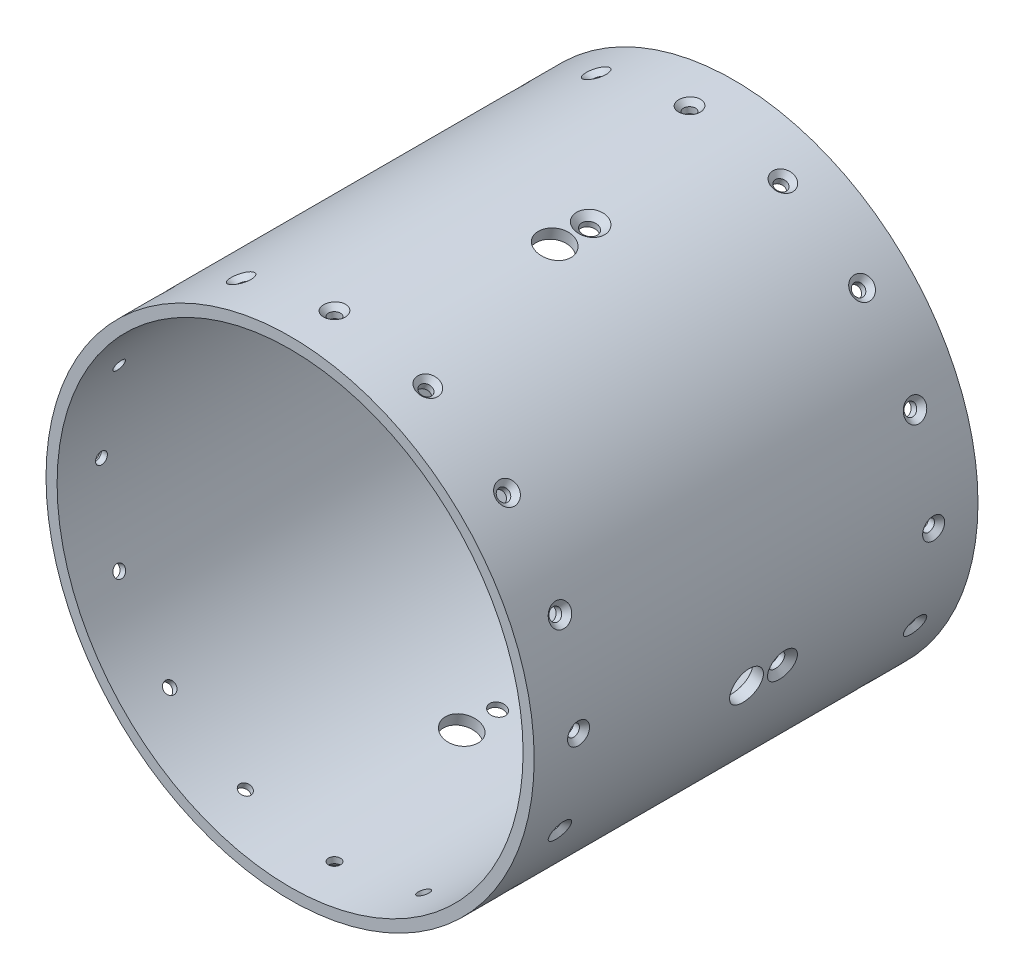
SolidWorks part; units mm, degrees
material "6061-T6 (SS)"
ref_plane "Front Plane" through (0, 0, 0) normal (0, 0, 1) x (1, 0, 0)
ref_plane "Top Plane" through (0, 0, 0) normal (0, 1, 0) x (1, 0, 0)
ref_plane "Right Plane" through (0, 0, 0) normal (1, 0, 0) x (0, 0, -1)
sketch "Sketch1" plane through (0, 0, 0) normal (0, 0, 1) x (1, 0, 0)
  circle A0 centre (0, 0) radius 66.675
  circle A1 centre (0, 0) radius 69.85
extrude "Extrude1" add sketch "Sketch1" along normal blind 127
sketch "Sketch4" plane through (0, 0, 0) normal (0, 0, -1) x (-1, 0, 0)
  circle A0 centre (0, 0) radius 66.675
sketch "Sketch5" plane through (0, 0, 127) normal (0, 0, 1) x (1, 0, 0)
  circle A0 centre (0, 0) radius 66.675
ref_plane "Plane1" through (0, 0, 12.7) normal (0, 0, 1) x (1, 0, 0)
ref_plane "Plane3" through (0, 0, 114.3) normal (0, 0, 1) x (1, 0, 0)
sketch "Sketch11" plane through (0, 0, 114.3) normal (0, 0, 1) x (1, 0, 0)
  line L0 (0, 0) -> (69.85, 0) construction
  circle A0 centre (0, 0) radius 69.85 construction
ref_plane "Plane4" through (69.85, 0, 114.3) normal (1, 0, 0) x (0, 0, -1)
hole_wizard "CSK for M3 Flat Head Machine Screw2" positions "Sketch13" profile "Sketch12" countersink size "M3" standard "Ansi Metric"
sketch "Sketch13" plane through (69.85, 0, 114.3) normal (1, 0, 0) x (0, 0, -1)
  point P1 (0, 0)
sketch "Sketch12" plane through (69.85, 0, 114.3) normal (0, 1, 0) x (0, 0, -1)
  line L0 (0, 0) -> (0, 13.2135)
  line L1 (0, 13.2135) -> (1.7, 12.192)
  line L2 (1.7, 12.192) -> (1.7, 1.45)
  line L3 (1.7, 1.45) -> (3.15, 0)
  line L5 (3.15, 0) -> (0, 0)
  line L6 (-1.7, 1.45) -> (-3.15, 0) construction
  line L10 (0, 13.2135) -> (-1.7, 12.192) construction
  line L11 (0, -6.35) -> (0, 107.95) construction
  dimension "Hole Dia." = 3.4
  dimension "Hole Depth" = 12.192
  dimension "Near C'Sink Dia." = 6.3
  dimension "Near C'Sink Angle" = 90
  dimension "Drill Angle" = 118
sketch "Sketch23" plane through (0, 0, 12.7) normal (0, 0, 1) x (1, 0, 0)
  line L0 (0, 0) -> (69.85, 0) construction
ref_plane "Plane7" through (69.85, 0, 12.7) normal (1, 0, 0) x (0, 0, -1)
hole_wizard "CSK for M3 Flat Head Machine Screw1" positions "Sketch29" profile "Sketch30" countersink size "M3" standard "Ansi Metric"
sketch "Sketch29" plane through (69.85, 0, 12.7) normal (1, 0, 0) x (0, 0, -1)
  point P1 (0, 0)
sketch "Sketch30" plane through (69.85, 0, 12.7) normal (0, 1, 0) x (0, 0, -1)
  line L0 (0, 0) -> (0, 13.2135)
  line L1 (0, 13.2135) -> (1.7, 12.192)
  line L2 (1.7, 12.192) -> (1.7, 1.45)
  line L3 (1.7, 1.45) -> (3.15, 0)
  line L5 (3.15, 0) -> (0, 0)
  line L6 (-1.7, 1.45) -> (-3.15, 0) construction
  line L10 (0, 13.2135) -> (-1.7, 12.192) construction
  line L11 (0, -6.35) -> (0, 107.95) construction
  dimension "Hole Dia." = 3.4
  dimension "Hole Depth" = 12.192
  dimension "Near C'Sink Dia." = 6.3
  dimension "Near C'Sink Angle" = 90
  dimension "Drill Angle" = 118
pattern_circular "CirPattern1" count 16 over 360 about axis through (0, 0, 127) along (0, 0, -1) of "CSK for M3 Flat Head Machine Screw2", "CSK for M3 Flat Head Machine Screw1"
ref_plane "Plane8" through (0, 0, 64.77) normal (0, 0, 1) x (1, 0, 0)
sketch "Sketch35" plane through (0, 0, 64.77) normal (0, 0, 1) x (1, 0, 0)
  line L0 (69.8153, 0) -> (68.4, 0) construction
  arc A0 (69.85, 0) -> (68.5079, -13.6271) centre (0, 0) cw
  circle A1 centre (0, 0) radius 69.85 construction
sketch "Sketch31" plane through (0, 0, 64.77) normal (0, 0, 1) x (1, 0, 0)
  line L0 (0, 0) -> (68.5079, -13.6271) construction
ref_plane "Plane6" through (68.5079, -13.6271, 64.77) normal (0.9808, -0.1951, 0) x (0.1951, 0.9808, 0)
sketch "Sketch15" plane through (68.5079, -13.6271, 64.77) normal (0.9808, -0.1951, 0) x (0.1951, 0.9808, 0)
  line L0 (0, 0.1207) -> (0, -10.16) construction
hole_wizard "3/8 (0.375) Diameter Hole1" positions "Sketch33" profile "Sketch32" hole size "3/8" standard "Ansi Inch"
sketch "Sketch33" plane through (68.5079, -13.6271, 64.77) normal (0.9808, -0.1951, 0) x (0.1951, 0.9808, 0)
  point P1 (0, 0.1207)
sketch "Sketch32" plane through (68.5079, -13.6271, 64.8907) normal (0, 0, 1) x (0.1951, 0.9808, 0)
  line L0 (0, 0) -> (0, 15.5616)
  line L1 (0, 15.5616) -> (4.7625, 12.7)
  line L2 (4.7625, 12.7) -> (4.7625, 0)
  line L5 (4.7625, 0) -> (0, 0)
  line L10 (0, 15.5616) -> (-4.7625, 12.7) construction
  line L11 (0, -6.35) -> (0, 107.95) construction
  dimension "Hole Dia." = 9.525
  dimension "Hole Depth" = 12.7
  dimension "Drill Angle" = 118
hole_wizard "CSK for #8 Flat Head Machine Screw (100)2" positions "Sketch21" profile "Sketch22" countersink size "#8" standard "Ansi Inch"
sketch "Sketch21" plane through (68.5079, -13.6271, 64.77) normal (0.9808, -0.1951, 0) x (0.1951, 0.9808, 0)
  point P1 (0, -10.16)
sketch "Sketch22" plane through (68.5079, -13.6271, 54.61) normal (0, 0, 1) x (0.1951, 0.9808, 0)
  line L0 (0, 0) -> (0, 13.5427)
  line L1 (0, 13.5427) -> (2.2479, 12.192)
  line L2 (2.2479, 12.192) -> (2.2479, 1.6518)
  line L3 (2.2479, 1.6518) -> (4.2164, 0)
  line L5 (4.2164, 0) -> (0, 0)
  line L6 (-2.2479, 1.6518) -> (-4.2164, 0) construction
  line L10 (0, 13.5427) -> (-2.2479, 12.192) construction
  line L11 (0, -6.35) -> (0, 107.95) construction
  dimension "Hole Dia." = 4.4958
  dimension "Hole Depth" = 12.192
  dimension "Near C'Sink Dia." = 8.4328
  dimension "Near C'Sink Angle" = 100
  dimension "Drill Angle" = 118
pattern_circular "CirPattern2" count 4 over 360 about axis through (0, 0, 127) along (0, 0, -1) of "CSK for #8 Flat Head Machine Screw (100)2", "3/8 (0.375) Diameter Hole1"
